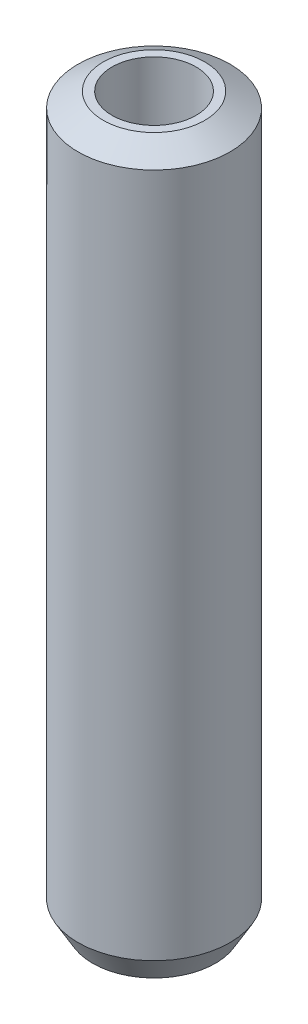
SolidWorks part; units mm, degrees
ref_plane "Front Plane" through (0, 0, 0) normal (0, 0, 1) x (1, 0, 0)
ref_plane "Top Plane" through (0, 0, 0) normal (0, 1, 0) x (1, 0, 0)
ref_plane "Right Plane" through (0, 0, 0) normal (1, 0, 0) x (0, 0, -1)
sketch "Sketch1" plane through (0, 0, 0) normal (0, 1, 0) x (1, 0, 0)
  circle A0 centre (0, 0) radius 12.5
  dimension "SHAFT_OD" = 25
extrude "Boss-Extrude1" add sketch "Sketch1" along normal blind 119.1374
sketch "Sketch2" plane through (0, 0, 0) normal (0, 1, 0) x (1, 0, 0)
  circle A0 centre (0, 0) radius 6.9084
  dimension "BORE_D" = 13.8168
extrude "Cut-Extrude1" cut sketch "Sketch2" along normal through all
chamfer "Chamfer1" distance 2.402 angle 60 2 edges at (0, 119.1374, 12.5) (0, 0, 12.5) first distance on face at (0, 119.1374, 12.5) first distance on face at (0, 0, 6.9084)
